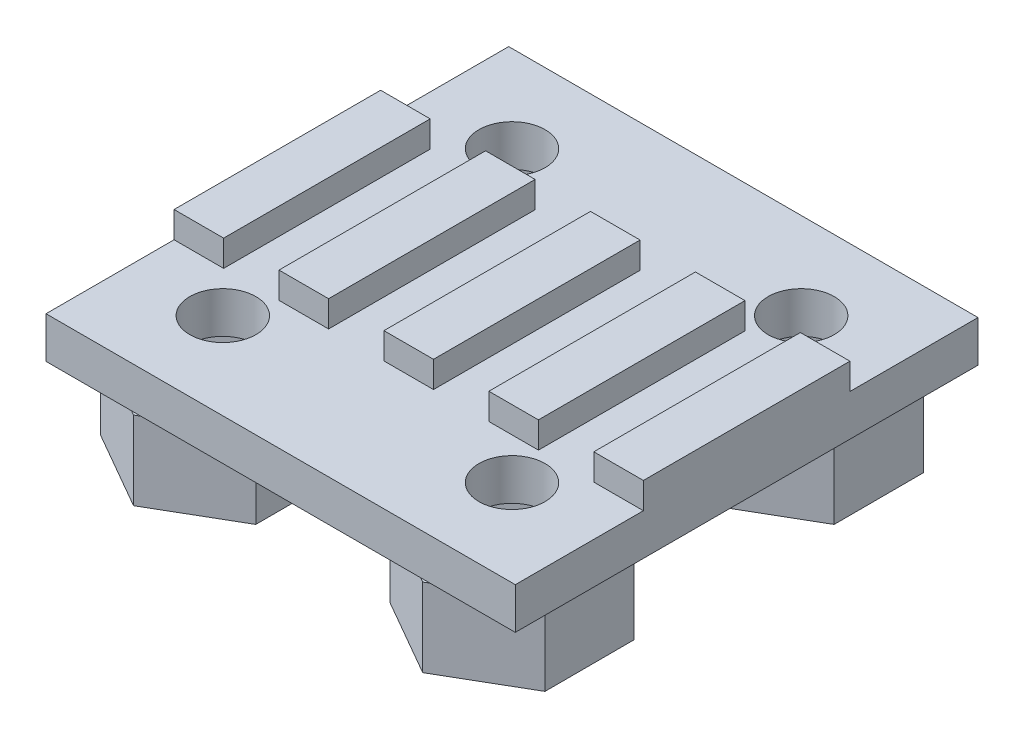
SolidWorks part; units mm, degrees
ref_plane "前视基准面" through (0, 0, 0) normal (0, 0, 1) x (1, 0, 0)
ref_plane "上视基准面" through (0, 0, 0) normal (0, 1, 0) x (1, 0, 0)
ref_plane "右视基准面" through (0, 0, 0) normal (1, 0, 0) x (0, 0, -1)
sketch "草图1" plane through (0, 0, 0) normal (0, 1, 0) x (1, 0, 0)
  line L1 (-11.36, 5) -> (11.36, 5)
  line L2 (-11.36, 5) -> (-11.36, -5)
  line L3 (-11.36, -5) -> (11.36, -5)
  line L4 (11.36, 5) -> (11.36, -5)
  line L5 (-11.36, 5) -> (11.36, -5) construction
  line L6 (-11.36, -5) -> (11.36, 5) construction
  point P0 (0, 0)
  dimension "D1" = 10
  dimension "D2" = 22.72
extrude "主体" add sketch "草图1" along normal blind 2
sketch "草图3" plane through (0, 2, 0) normal (0, 1, 0) x (1, 0, 0)
  line L0 (-11.36, -5) -> (11.36, -5) construction
  line L1 (-1.2, 5) -> (1.2, 5)
  line L2 (-1.2, 5) -> (-1.2, -5)
  line L3 (-1.2, -5) -> (1.2, -5)
  line L4 (1.2, 5) -> (1.2, -5)
  line L5 (-1.2, 5) -> (1.2, -5) construction
  line L6 (-1.2, -5) -> (1.2, 5) construction
  point P0 (0, 0)
  dimension "D1" = 2.4
extrude "凸台-拉伸2" add sketch "草图3" along normal blind 1.27
pattern_linear "阵列(线性)1" count 3 spacing 5.08 along (1, 0, 0) count 3 spacing 5.08 along (-1, 0, 0) of "凸台-拉伸2" pattern seed only yes
sketch "草图4" plane through (0, 0, 0) normal (0, 0, 1) x (1, 0, 0)
  line L0 (8.96, 2) -> (6.28, 2) construction
  line L1 (11.36, 2) -> (-11.36, 2)
  line L2 (11.36, 2) -> (11.36, 0)
  line L3 (11.36, 0) -> (-11.36, 0)
  line L4 (-11.36, 2) -> (-11.36, 0)
  line L5 (11.36, 0) -> (-11.36, 0) construction
  line L6 (-11.36, 3.27) -> (-11.36, 0) construction
  line L7 (11.36, 3.27) -> (11.36, 0) construction
extrude "凸台-拉伸3" add sketch "草图4" along normal blind 6.2 from surface starting at face at (0, 2.435, 5)
extrude "凸台-拉伸4" add sketch "草图4<2>" against normal blind 6.2 from surface starting at face at (0, 2.435, -5)
sketch "草图4<2>" plane through (0, 0, 0) normal (0, 0, 1) x (1, 0, 0) same geometry as "草图4"
sketch "草图6" plane through (0, 0, 0) normal (0, -1, 0) x (-1, 0, 0)
  line L1 (7, -7) -> (-7, -7) construction
  line L2 (7, -7) -> (7, 7) construction
  line L3 (7, 7) -> (-7, 7) construction
  line L4 (-7, -7) -> (-7, 7) construction
  line L5 (7, -7) -> (-7, 7) construction
  line L6 (7, 7) -> (-7, -7) construction
  point P7 (-7, -7)
  point P8 (-7, 7)
  point P9 (7, 7)
  point P13 (7, -7)
  dimension "D1" = 14
  dimension "D2" = 14
sketch "草图5" plane through (0, 0, 0) normal (0, -1, 0) x (1, 0, 0)
  line L1 (7.0059, 10.1754) -> (4.253, 8.5928)
  line L2 (4.253, 8.5928) -> (4.2471, 5.4174)
  line L3 (4.2471, 5.4174) -> (6.9941, 3.8246)
  line L4 (6.9941, 3.8246) -> (9.747, 5.4072)
  line L5 (9.747, 5.4072) -> (9.7529, 8.5826)
  line L6 (9.7529, 8.5826) -> (7.0059, 10.1754)
  circle A0 centre (7, 7) radius 2.75 construction
  dimension "D1" = 5.5
extrude "拉伸-薄壁1" add sketch "草图5" along normal blind 3.8 thin thin type one direction wall 1
pattern_sketch "草图阵列1" of "拉伸-薄壁1" driven by "草图6"
hole_wizard "M3 间隙孔1" positions "草图7" profile "草图8" hole size "M3" standard "ISO" end condition up to next
sketch "草图7" plane through (0, 2, 0) normal (0, 1, 0) x (1, 0, 0)
  point P0 (7, -7)
sketch "草图8" plane through (7, 2, 7) normal (1, 0, 0) x (0, 0, 1)
  line L0 (0, 0) -> (0, 2)
  line L1 (0, 2) -> (1.6, 2)
  line L2 (1.6, 2) -> (1.6, 0)
  line L5 (1.6, 0) -> (0, 0)
  line L11 (0, -6.35) -> (0, 107.95) construction
  dimension "通孔孔直径" = 3.2
  dimension "通孔孔深度" = 2
pattern_sketch "草图阵列2" of "M3 间隙孔1" driven by "草图6"
